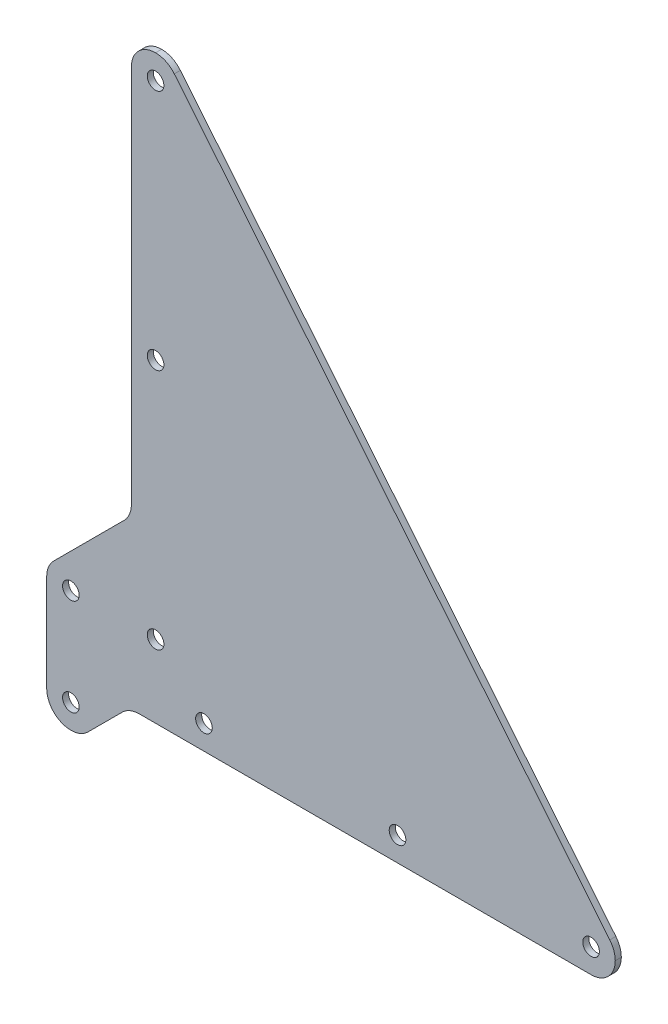
SolidWorks part; units mm, degrees
ref_plane "Front Plane" through (0, 0, 0) normal (0, 0, 1) x (1, 0, 0)
ref_plane "Top Plane" through (0, 0, 0) normal (0, 1, 0) x (1, 0, 0)
ref_plane "Right Plane" through (0, 0, 0) normal (1, 0, 0) x (0, 0, -1)
sketch "Sketch1" plane through (0, 0, 0) normal (0, 0, 1) x (1, 0, 0)
  line L0 (-28.575, 2.6303) -> (-28.575, -31.75)
  line L1 (-28.575, -31.75) -> (-19.5947, -31.75)
  line L2 (-19.5947, -31.75) -> (-6.8947, -19.05)
  line L3 (-6.8947, -19.05) -> (120.65, -19.05)
  line L4 (120.65, -19.05) -> (120.65, -10.4333)
  line L5 (120.65, -10.4333) -> (3.0091, 133.35)
  line L6 (3.0091, 133.35) -> (-6.35, 133.35)
  line L7 (-6.35, 133.35) -> (-6.35, 24.8553)
  line L8 (-6.35, 24.8553) -> (-28.575, 2.6303)
  circle A0 centre (0, 0) radius 2.1828
  circle A1 centre (0, 63.5) radius 2.1828
  circle A2 centre (12.7, -12.7) radius 2.1828
  circle A3 centre (63.5, -12.7) radius 2.1828
  circle A4 centre (-22.225, 0) radius 2.1828
  circle A5 centre (-22.225, -25.4) radius 2.1828
  circle A6 centre (0, 127) radius 2.1828
  circle A7 centre (114.3, -12.7) radius 2.1828
  dimension "D8" = 4.3656
  dimension "D9" = 4.3656
  dimension "D10" = 4.3656
  dimension "D11" = 4.3656
  dimension "D12" = 4.3656
  dimension "D13" = 4.3656
  dimension "D14" = 4.3656
  dimension "D16" = 4.3656
  dimension "D1" = 25.4
  dimension "D2" = 22.225
  dimension "D3" = 12.7
  dimension "D4" = 12.7
  dimension "D5" = 50.8
  dimension "D6" = 63.5
  dimension "D7" = 63.5
  dimension "D15" = 50.8
  dimension "D17" = 6.35
  dimension "D18" = 6.35
  dimension "D19" = 6.35
  dimension "D20" = 6.35
  dimension "D21" = 6.35
  dimension "D22" = 6.35
  dimension "D23" = 6.35
  dimension "D24" = 6.35
  dimension "D25" = 6.35
  dimension "D26" = 135
  dimension "D27" = 6.35
  dimension "D28" = 135
extrude "Boss-Extrude1" add sketch "Sketch1" along normal mid plane 1.5875
fillet "Fillet1" radius 6.35 9 edges at (120.65, -19.05, 0) (120.65, -10.4333, 0) (-6.8947, -19.05, 0) (-19.5947, -31.75, 0) (-28.575, -31.75, 0) (-28.575, 2.6303, 0) (-6.35, 24.8553, 0) (3.0091, 133.35, 0) (-6.35, 133.35, 0)
